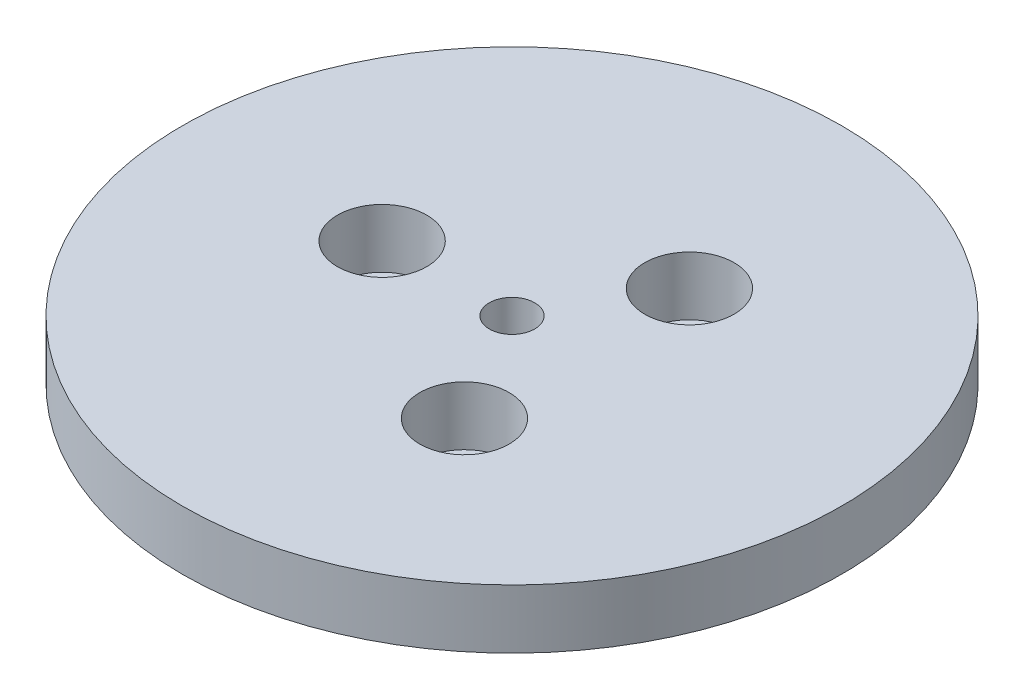
SolidWorks part; units mm, degrees
ref_plane "Front Plane" through (0, 0, 0) normal (0, 0, 1) x (1, 0, 0)
ref_plane "Top Plane" through (0, 0, 0) normal (0, 1, 0) x (1, 0, 0)
ref_plane "Right Plane" through (0, 0, 0) normal (1, 0, 0) x (0, 0, -1)
sketch "Sketch1" plane through (0, 0, 0) normal (0, 1, 0) x (1, 0, 0)
  circle A0 centre (0, 0) radius 72.5
  dimension "FLANGE_OD" = 145
extrude "Boss-Extrude1" add sketch "Sketch1" along normal blind 13
sketch "Sketch2" plane through (0, 0, 0) normal (0, 1, 0) x (1, 0, 0)
  circle A0 centre (0, 0) radius 5
  dimension "BORE_D" = 10
extrude "Cut-Extrude1" cut sketch "Sketch2" along normal through all
sketch "Sketch3" plane through (0, 13, 0) normal (0, 1, 0) x (1, 0, 0)
  circle A0 centre (0, 0) radius 28.5731 construction
  circle A1 centre (-28.5731, 0) radius 9.8308
  dimension "BOLT_D" = 19.6617
  dimension "BOLT_PCD" = 57.1461
extrude "Cut-Extrude2" cut sketch "Sketch3" against normal blind 12.9258
pattern_circular "CirPattern1" count 3 over 360 about axis through (0, 0, 0) along (0, 1, 0) of "Cut-Extrude2"
